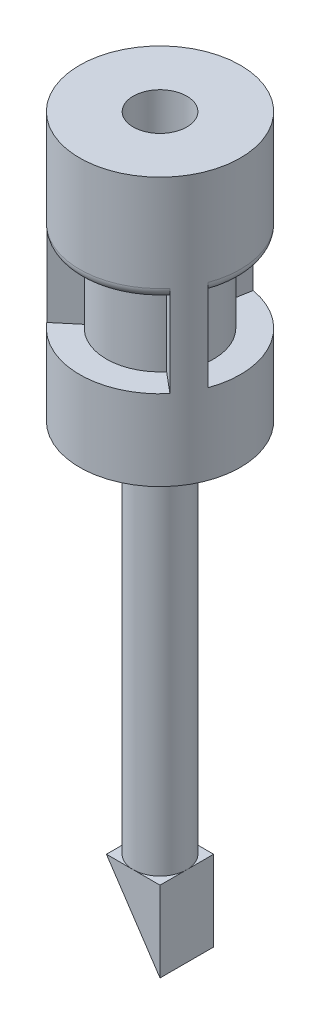
SolidWorks part; units mm, degrees
ref_plane "Front Plane" through (0, 0, 0) normal (0, 0, 1) x (1, 0, 0)
ref_plane "Top Plane" through (0, 0, 0) normal (0, 1, 0) x (1, 0, 0)
ref_plane "Right Plane" through (0, 0, 0) normal (1, 0, 0) x (0, 0, -1)
sketch "Sketch3" plane through (0, 0, 0) normal (0, 0, 1) x (1, 0, 0)
  line L0 (-10, 15) -> (0, 0)
  line L2 (0, 0) -> (0, 15)
  line L4 (-10, 15) -> (-10, 55) construction
  line L5 (-10, 55) -> (0, 55) construction
  line L6 (0, 55) -> (0, 15) construction
  line L7 (-10, 15) -> (0, 15)
  dimension "D1" = 15
  dimension "D2" = 10
  dimension "D3" = 40
extrude "Boss-Extrude2" add sketch "Sketch3" along normal mid plane 10
sketch "Sketch7" plane through (0, 0, 0) normal (0, 0, 1) x (1, 0, 0)
  line L0 (-5, 15) -> (-5, 62.0793) construction
  line L2 (-5, 15) -> (0, 15)
  line L3 (0, 15) -> (0, 85)
  line L4 (0, 85) -> (-5, 85)
  line L5 (-5, 85) -> (-5, 15)
  line L7 (0, 15) -> (-10, 15) construction
  dimension "D1" = 70
  dimension "D2" = 5
revolve "Revolve3" add sketch "Sketch7" angle 360 about L0
ref_plane "Plane1" through (0, 90, 0) normal (0, 1, 0) x (1, 0, 0)
sketch "Sketch5" plane through (0, 0, 0) normal (0, 0, 1) x (1, 0, 0)
  line L0 (-5, 85) -> (-5, 119.3656) construction
  line L1 (-5, 85) -> (-5, 95)
  line L3 (5, 100) -> (5, 115)
  line L4 (10, 135) -> (0, 135)
  line L5 (0, 135) -> (0, 95)
  line L6 (-5, 85) -> (10, 85)
  line L8 (10, 135) -> (10, 115)
  line L9 (10, 115) -> (5, 115)
  line L11 (10, 85) -> (10, 100)
  line L12 (10, 100) -> (5, 100)
  line L13 (0, 85) -> (-10, 85) construction
  line L14 (0, 15) -> (0, 85) construction
  line L15 (-5, 95) -> (0, 95)
  dimension "D1" = 50
  dimension "D2" = 20
  dimension "D3" = 10
  dimension "D4" = 30
  dimension "D5" = 20
  dimension "D6" = 15
  dimension "D7" = 5
  dimension "D8" = 10
revolve "Revolve2" add sketch "Sketch5" angle 360 about L0
sketch "Sketch6" plane through (0, 100, 0) normal (0, 1, 0) x (1, 0, 0)
  line L0 (-5, 0) -> (-5, 24.9132) construction
  line L1 (-6.3024, 7.3861) -> (-7.6047, 14.7721)
  line L2 (-3.6976, 7.3861) -> (-2.3953, 14.7721)
  line L3 (-5, 0) -> (-7.6047, 14.7721) construction
  line L4 (2.0477, -2.5652) -> (9.0954, -5.1303)
  line L5 (0.7453, -4.8209) -> (6.4907, -9.6418)
  line L6 (-10.7453, -4.8209) -> (-16.4907, -9.6418)
  line L7 (-12.0477, -2.5652) -> (-19.0954, -5.1303)
  circle A1 centre (-5, 0) radius 15
  arc A2 (-19.0954, -5.1303) -> (-16.4907, -9.6418) centre (-5, 0) ccw
  arc A3 (-2.3953, 14.7721) -> (-7.6047, 14.7721) centre (-5, 0) ccw
  arc A4 (6.4907, -9.6418) -> (9.0954, -5.1303) centre (-5, 0) ccw
  arc A5 (-12.0477, -2.5652) -> (-10.7453, -4.8209) centre (-5, 0) ccw
  arc A6 (-3.6976, 7.3861) -> (-6.3024, 7.3861) centre (-5, 0) ccw
  arc A7 (0.7453, -4.8209) -> (2.0477, -2.5652) centre (-5, 0) ccw
  dimension "D4" = 7.5
  dimension "D2" = 3
  dimension "D3" = 10
  dimension "D1" = 0
extrude "Boss-Extrude3" add sketch "Sketch6" along normal up to next
fillet "Fillet1" radius 2 3 edges at (7.9904, 115, -7.5) (-17.9904, 115, -7.5) (-5, 115, 15)
